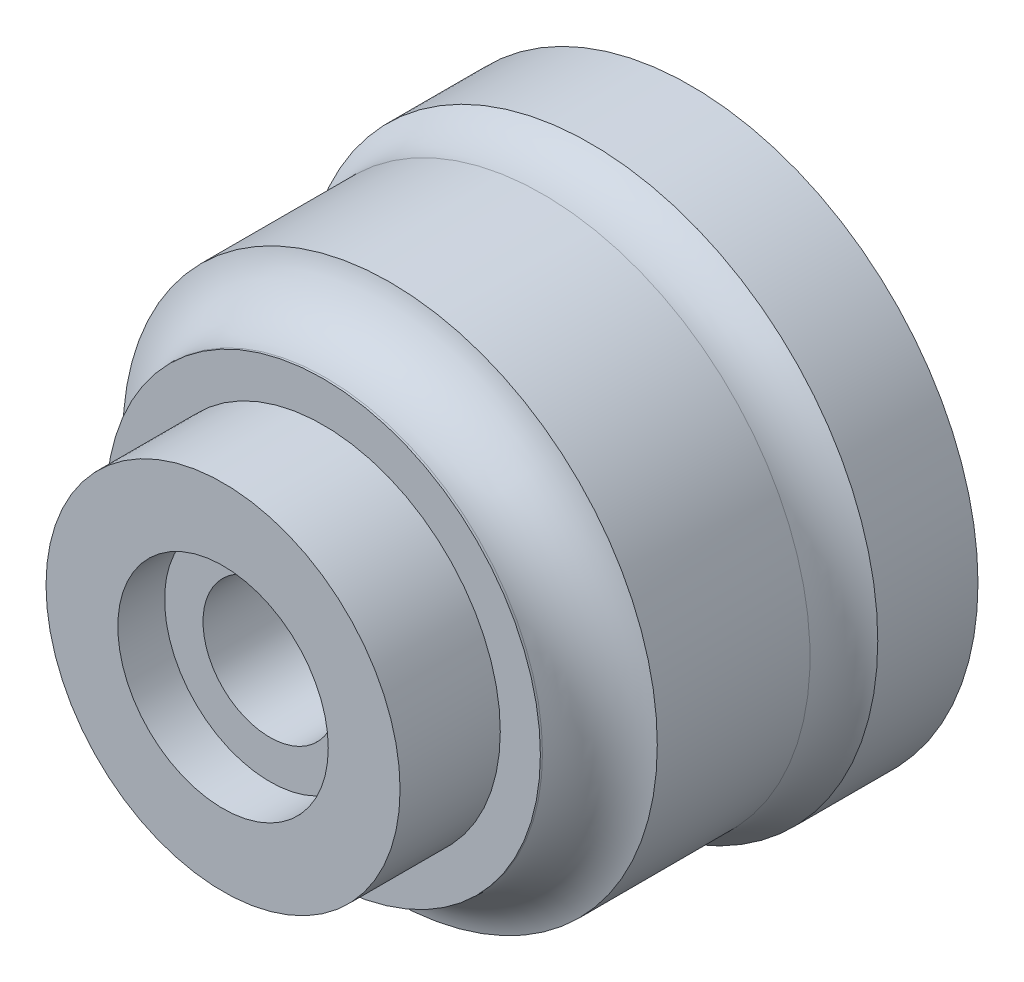
SolidWorks part; units mm, degrees
material "Сплав 1060"
ref_plane "Спереди" through (0, 0, 0) normal (0, 0, 1) x (1, 0, 0)
ref_plane "Сверху" through (0, 0, 0) normal (0, 1, 0) x (1, 0, 0)
ref_plane "Справа" through (0, 0, 0) normal (1, 0, 0) x (0, 0, -1)
sketch "Эскиз1" plane through (0, 0, 0) normal (0, 0, 1) x (1, 0, 0)
  circle A0 centre (0, 0) radius 18.9
  circle A1 centre (0, 0) radius 43
  dimension "D1" = 37.8
  dimension "D2" = 86
extrude "Вытянуть1" add sketch "Эскиз1" along normal blind 15
sketch "Эскиз2" plane through (0, 0, 0) normal (0, 0, 1) x (1, 0, 0)
  circle A0 centre (5.2094, 29.5442) radius 4.5
  circle A1 centre (-18.5481, 23.579) radius 3
  circle A2 centre (-29.5442, 5.2094) radius 4.5
  circle A3 centre (-5.2094, -29.5442) radius 4.5
  circle A4 centre (18.5481, -23.579) radius 3
  circle A5 centre (29.5442, -5.2094) radius 4.5
  dimension "D1" = 9
  dimension "D2" = 6
sketch "Эскиз3" plane through (0, 0, 15) normal (0, 0, 1) x (1, 0, 0)
  circle A0 centre (0, 0) radius 19
  circle A1 centre (0, 0) radius 40
  dimension "D1" = 38
  dimension "D2" = 80
extrude "Вытянуть2" add sketch "Эскиз3" along normal blind 30
sketch "Эскиз7" plane through (0, 0, 45) normal (0, 0, 1) x (1, 0, 0)
  circle A0 centre (0, 0) radius 32.5
  circle A2 centre (0, 0) radius 10
  dimension "D1" = 65
  dimension "D2" = 20
extrude "Вытянуть3" add sketch "Эскиз7" along normal blind 10
fillet "Скругление3" radius 10 1 edges at (40, 0, 15)
extrude "Вытянуть4" [suppressed] cut sketch "Эскиз2" along normal blind 35
ref_plane "Плоскость1" through (0, 0, 48) normal (0, 0, 1) x (1, 0, 0)
sketch "Эскиз9" plane through (0, 0, 48) normal (0, 0, 1) x (1, 0, 0)
  circle A0 centre (0, 0) radius 10
  circle A1 centre (0, 0) radius 16
  dimension "D1" = 20
  dimension "D2" = 32
extrude "Вытянуть6" add sketch "Эскиз9" along normal blind 7 separate body
sketch "Эскиз10" plane through (0, 0, 55) normal (0, 0, 1) x (1, 0, 0)
  circle A0 centre (0, 0) radius 26.5
  circle A2 centre (0, 0) radius 10
  dimension "D1" = 20
  dimension "D2" = 53
extrude "Вытянуть7" add sketch "Эскиз10" along normal blind 15
sketch "Эскиз12" plane through (0, 0, 70) normal (0, 0, 1) x (1, 0, 0)
  circle A0 centre (0, 0) radius 15.75
  dimension "D1" = 31.5
extrude "Вытянуть8" cut sketch "Эскиз12" against normal blind 7
fillet "Скругление4" radius 10 1 edges at (32.5, 0, 45)
